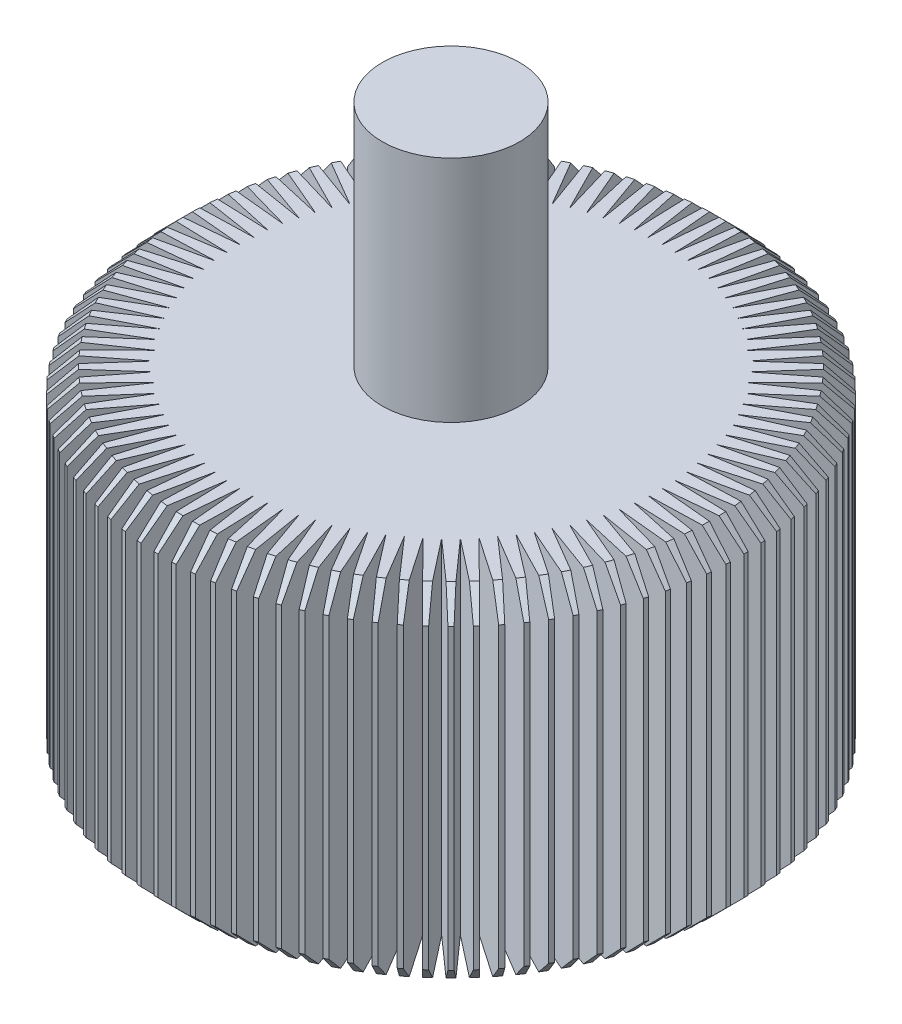
SolidWorks part; units mm, degrees
ref_plane "前视" through (0, 0, 0) normal (0, 0, 1) x (1, 0, 0)
ref_plane "上视" through (0, 0, 0) normal (0, 1, 0) x (1, 0, 0)
ref_plane "右视" through (0, 0, 0) normal (1, 0, 0) x (0, 0, -1)
sketch "草图1" plane through (0, 0, 0) normal (0, 1, 0) x (1, 0, 0)
  circle A0 centre (0, 0) radius 12.5
  dimension "D1" = 25
extrude "凸台-拉伸1" add sketch "草图1" along normal blind 15
sketch "草图2" plane through (0, 15, 0) normal (0, 1, 0) x (1, 0, 0)
  circle A0 centre (0, 0) radius 3
  dimension "D1" = 6
extrude "凸台-拉伸2" add sketch "草图2" along normal blind 10
chamfer "倒角1" distance 1 angle 45 2 edges at (0, 0, 12.5) (0, 15, 12.5)
sketch "草图3" plane through (0, 15, 0) normal (0, 1, 0) x (1, 0, 0)
  line L0 (0, 0) -> (0, 10) construction
  line L1 (-0.2984, 12.4964) -> (0, 9.2)
  line L2 (0.2984, 12.4964) -> (0, 9.2)
  circle A0 centre (0, 0) radius 12.5 construction
  arc A1 (0.2984, 12.4964) -> (-0.2984, 12.4964) centre (0, 0) ccw
extrude "切除-拉伸1" cut sketch "草图3" against normal up to next
pattern_circular "阵列(圆周)1" count 100 over 360 about axis through (0, 15, 0) along (0, -1, 0) of "切除-拉伸1"
